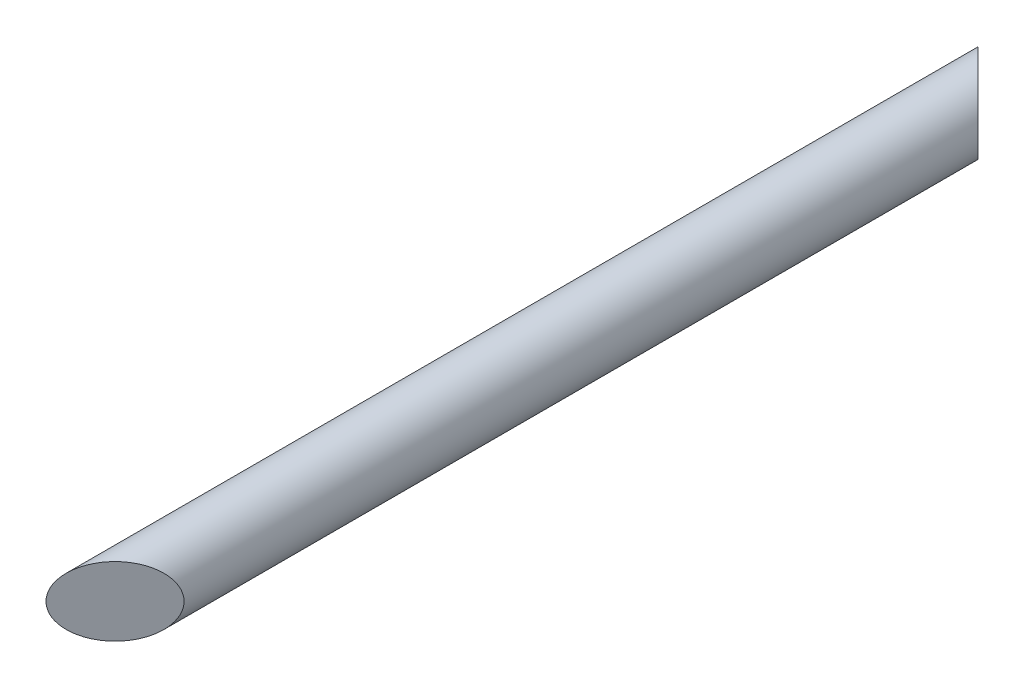
SolidWorks part; units mm, degrees
ref_plane "Front Plane" through (0, 0, 0) normal (0, 0, 1) x (1, 0, 0)
ref_plane "Top Plane" through (0, 0, 0) normal (0, 1, 0) x (1, 0, 0)
ref_plane "Right Plane" through (0, 0, 0) normal (1, 0, 0) x (0, 0, -1)
sketch "Sketch1" plane through (0, 0, 0) normal (0, 0, 1) x (1, 0, 0)
  circle A0 centre (0, 0) radius 30
  dimension "D1" = 60
extrude "Boss-Extrude2" add sketch "Sketch1" along normal blind 810 contours A0
ref_plane "Plane1" through (0, 40, 0) normal (0, 1, 0) x (1, 0, 0)
sketch "Sketch3" plane through (0, 40, 0) normal (0, 1, 0) x (1, 0, 0)
  line L0 (-30, 0) -> (30, -60)
  line L1 (30, -810) -> (30, 0) construction
  line L2 (30, -60) -> (30, 0)
  line L3 (30, 0) -> (-30, 0)
  dimension "D1" = 60
  dimension "D2" = 60
sketch "Sketch4" plane through (0, 40, 0) normal (0, 1, 0) x (1, 0, 0)
  line L0 (-30, -810) -> (30, -810)
  line L1 (30, -810) -> (30, -750)
  line L2 (30, -810) -> (30, 0) construction
  line L3 (30, -750) -> (-30, -810)
  dimension "D1" = 60
extrude "Cut-Extrude1" cut sketch "Sketch4" against normal blind 70
extrude "Cut-Extrude2" cut sketch "Sketch3" against normal blind 70 contours L3 L0 L2
